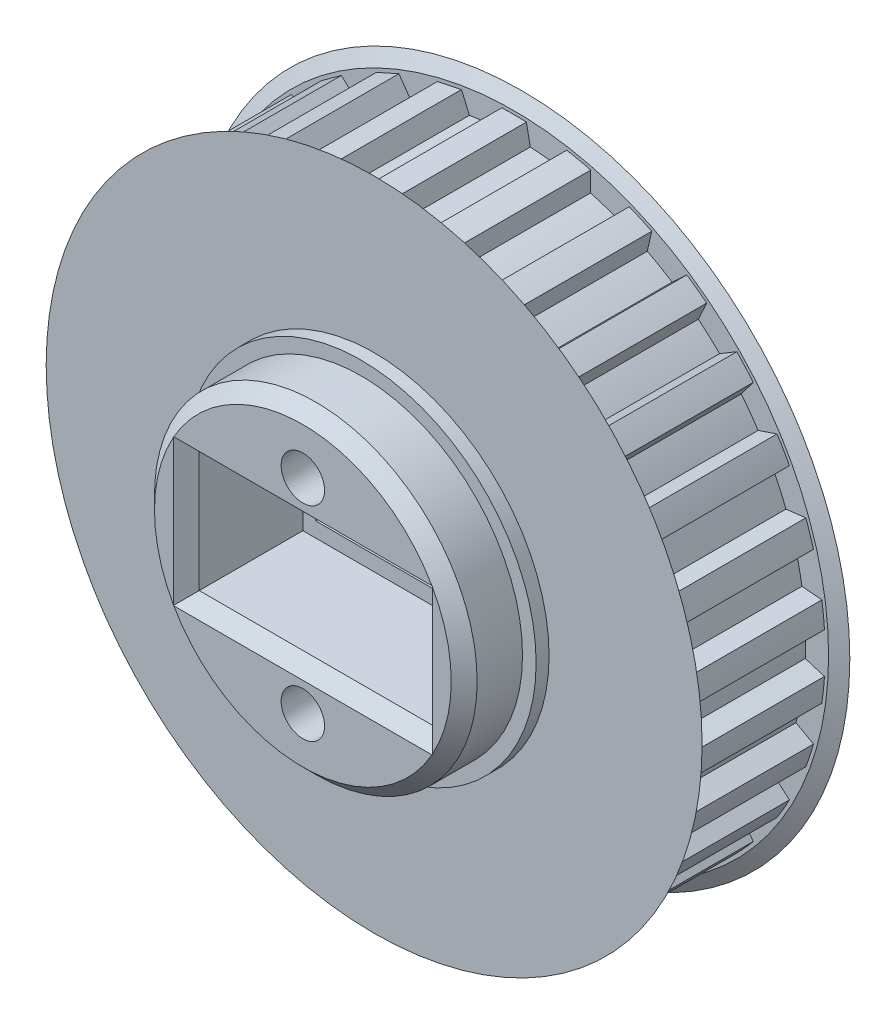
SolidWorks part; units mm, degrees
material "ABS"
ref_plane "Alzado" through (0, 0, 0) normal (0, 0, 1) x (1, 0, 0)
ref_plane "Planta" through (0, 0, 0) normal (0, 1, 0) x (1, 0, 0)
ref_plane "Vista lateral" through (0, 0, 0) normal (1, 0, 0) x (0, 0, -1)
sketch "Croquis1" plane through (0, 0, 0) normal (0, 0, 1) x (1, 0, 0)
  line L0 (0, 0) -> (0, 14.5885) construction
  line L1 (-0.95, 23.9812) -> (-1.25, 22.4653)
  line L2 (0.95, 23.9812) -> (1.25, 22.4653)
  line L3 (5.9152, 23.2596) -> (5.8935, 21.7144)
  line L4 (4.0567, 23.6547) -> (3.4481, 22.2342)
  line L5 (10.6219, 21.5215) -> (10.2794, 20.0146)
  line L6 (8.8862, 22.2943) -> (7.9955, 21.0314)
  line L7 (14.8644, 18.8428) -> (14.216, 17.44)
  line L8 (13.3272, 19.9596) -> (12.1935, 18.9095)
  line L9 (18.4572, 15.3406) -> (17.5313, 14.1033)
  line L10 (17.1858, 16.7525) -> (15.8585, 15.9611)
  line L11 (21.2433, 11.1679) -> (20.0805, 10.1501)
  line L12 (20.2933, 12.8133) -> (18.8305, 12.3152)
  line L13 (23.101, 6.5071) -> (21.752, 5.7533)
  line L14 (22.5139, 8.3141) -> (20.9795, 8.131)
  line L15 (23.9491, 1.5619) -> (22.4728, 1.1051)
  line L16 (23.7505, 3.4515) -> (22.2115, 3.5914)
  line L17 (23.7505, -3.4515) -> (22.2115, -3.5914)
  line L18 (23.9491, -1.5619) -> (22.4728, -1.1051)
  line L19 (22.5139, -8.3141) -> (20.9795, -8.131)
  line L20 (23.101, -6.5071) -> (21.752, -5.7533)
  line L21 (20.2933, -12.8133) -> (18.8305, -12.3152)
  line L22 (21.2433, -11.1679) -> (20.0805, -10.1501)
  line L23 (17.1858, -16.7525) -> (15.8585, -15.9611)
  line L24 (18.4572, -15.3406) -> (17.5313, -14.1033)
  line L25 (13.3272, -19.9596) -> (12.1935, -18.9095)
  line L26 (14.8644, -18.8428) -> (14.216, -17.44)
  line L27 (8.8862, -22.2943) -> (7.9955, -21.0314)
  line L28 (10.6219, -21.5215) -> (10.2794, -20.0146)
  line L29 (4.0567, -23.6547) -> (3.4481, -22.2342)
  line L30 (5.9152, -23.2596) -> (5.8935, -21.7144)
  line L31 (-0.95, -23.9812) -> (-1.25, -22.4653)
  line L32 (0.95, -23.9812) -> (1.25, -22.4653)
  line L33 (-5.9152, -23.2596) -> (-5.8935, -21.7144)
  line L34 (-4.0567, -23.6547) -> (-3.4481, -22.2342)
  line L35 (-10.6219, -21.5215) -> (-10.2794, -20.0146)
  line L36 (-8.8862, -22.2943) -> (-7.9955, -21.0314)
  line L37 (-14.8644, -18.8428) -> (-14.216, -17.44)
  line L38 (-13.3272, -19.9596) -> (-12.1935, -18.9095)
  line L39 (-18.4572, -15.3406) -> (-17.5313, -14.1033)
  line L40 (-17.1858, -16.7525) -> (-15.8585, -15.9611)
  line L41 (-21.2433, -11.1679) -> (-20.0805, -10.1501)
  line L42 (-20.2933, -12.8133) -> (-18.8305, -12.3152)
  line L43 (-23.101, -6.5071) -> (-21.752, -5.7533)
  line L44 (-22.5139, -8.3141) -> (-20.9795, -8.131)
  line L45 (-23.9491, -1.5619) -> (-22.4728, -1.1051)
  line L46 (-23.7505, -3.4515) -> (-22.2115, -3.5914)
  line L47 (-23.7505, 3.4515) -> (-22.2115, 3.5914)
  line L48 (-23.9491, 1.5619) -> (-22.4728, 1.1051)
  line L49 (-22.5139, 8.3141) -> (-20.9795, 8.131)
  line L50 (-23.101, 6.5071) -> (-21.752, 5.7533)
  line L51 (-20.2933, 12.8133) -> (-18.8305, 12.3152)
  line L52 (-21.2433, 11.1679) -> (-20.0805, 10.1501)
  line L53 (-17.1858, 16.7525) -> (-15.8585, 15.9611)
  line L54 (-18.4572, 15.3406) -> (-17.5313, 14.1033)
  line L55 (-13.3272, 19.9596) -> (-12.1935, 18.9095)
  line L56 (-14.8644, 18.8428) -> (-14.216, 17.44)
  line L57 (-18.4572, 15.3406) -> (-17.1858, 16.7525)
  line L58 (-14.8644, 18.8428) -> (-13.3272, 19.9596)
  line L59 (-8.8862, 22.2943) -> (-7.9955, 21.0314)
  line L60 (-10.6219, 21.5215) -> (-10.2794, 20.0146)
  line L61 (-4.0567, 23.6547) -> (-3.4481, 22.2342)
  line L62 (-5.9152, 23.2596) -> (-5.8935, 21.7144)
  line L63 (-10.6219, 21.5215) -> (-8.8862, 22.2943)
  line L64 (-5.9152, 23.2596) -> (-4.0567, 23.6547)
  arc A0 (-17.5313, 14.1033) -> (-18.8305, 12.3152) centre (0, 0) ccw
  arc A1 (3.4481, 22.2342) -> (1.25, 22.4653) centre (0, 0) ccw
  arc A2 (-14.216, 17.44) -> (-15.8585, 15.9611) centre (0, 0) ccw
  arc A3 (-5.8935, 21.7144) -> (-7.9955, 21.0314) centre (0, 0) ccw
  arc A4 (-10.2794, 20.0146) -> (-12.1935, 18.9095) centre (0, 0) ccw
  arc A8 (-20.2933, 12.8133) -> (-21.2433, 11.1679) centre (0, 0) ccw
  arc A9 (-22.5139, 8.3141) -> (-23.101, 6.5071) centre (0, 0) ccw
  arc A10 (-23.7505, 3.4515) -> (-23.9491, 1.5619) centre (0, 0) ccw
  arc A11 (5.9152, 23.2596) -> (4.0567, 23.6547) centre (0, 0) ccw
  arc A12 (0.95, 23.9812) -> (-0.95, 23.9812) centre (0, 0) ccw
  arc A16 (10.6219, 21.5215) -> (8.8862, 22.2943) centre (0, 0) ccw
  arc A17 (14.8644, 18.8428) -> (13.3272, 19.9596) centre (0, 0) ccw
  arc A18 (18.4572, 15.3406) -> (17.1858, 16.7525) centre (0, 0) ccw
  arc A19 (21.2433, 11.1679) -> (20.2933, 12.8133) centre (0, 0) ccw
  arc A20 (23.101, 6.5071) -> (22.5139, 8.3141) centre (0, 0) ccw
  arc A21 (23.9491, 1.5619) -> (23.7505, 3.4515) centre (0, 0) ccw
  arc A22 (23.7505, -3.4515) -> (23.9491, -1.5619) centre (0, 0) ccw
  arc A23 (22.5139, -8.3141) -> (23.101, -6.5071) centre (0, 0) ccw
  arc A24 (20.2933, -12.8133) -> (21.2433, -11.1679) centre (0, 0) ccw
  arc A25 (17.1858, -16.7525) -> (18.4572, -15.3406) centre (0, 0) ccw
  arc A26 (-0.95, -23.9812) -> (0.95, -23.9812) centre (0, 0) ccw
  arc A27 (-5.9152, -23.2596) -> (-4.0567, -23.6547) centre (0, 0) ccw
  arc A28 (-10.6219, -21.5215) -> (-8.8862, -22.2943) centre (0, 0) ccw
  arc A29 (-18.4572, -15.3406) -> (-17.1858, -16.7525) centre (0, 0) ccw
  arc A30 (-21.2433, -11.1679) -> (-20.2933, -12.8133) centre (0, 0) ccw
  arc A31 (-23.101, -6.5071) -> (-22.5139, -8.3141) centre (0, 0) ccw
  arc A32 (-23.9491, -1.5619) -> (-23.7505, -3.4515) centre (0, 0) ccw
  arc A33 (4.0567, -23.6547) -> (5.9152, -23.2596) centre (0, 0) ccw
  arc A34 (8.8862, -22.2943) -> (10.6219, -21.5215) centre (0, 0) ccw
  arc A35 (13.3272, -19.9596) -> (14.8644, -18.8428) centre (0, 0) ccw
  arc A36 (7.9955, 21.0314) -> (5.8935, 21.7144) centre (0, 0) ccw
  arc A37 (12.1935, 18.9095) -> (10.2794, 20.0146) centre (0, 0) ccw
  arc A39 (-1.25, 22.4653) -> (-3.4481, 22.2342) centre (0, 0) ccw
  arc A43 (15.8585, 15.9611) -> (14.216, 17.44) centre (0, 0) ccw
  arc A44 (18.8305, 12.3152) -> (17.5313, 14.1033) centre (0, 0) ccw
  arc A45 (20.9795, 8.131) -> (20.0805, 10.1501) centre (0, 0) ccw
  arc A46 (22.2115, 3.5914) -> (21.752, 5.7533) centre (0, 0) ccw
  arc A47 (22.4728, -1.1051) -> (22.4728, 1.1051) centre (0, 0) ccw
  arc A48 (21.752, -5.7533) -> (22.2115, -3.5914) centre (0, 0) ccw
  arc A49 (20.0805, -10.1501) -> (20.9795, -8.131) centre (0, 0) ccw
  arc A50 (17.5313, -14.1033) -> (18.8305, -12.3152) centre (0, 0) ccw
  arc A51 (14.216, -17.44) -> (15.8585, -15.9611) centre (0, 0) ccw
  arc A52 (10.2794, -20.0146) -> (12.1935, -18.9095) centre (0, 0) ccw
  arc A53 (5.8935, -21.7144) -> (7.9955, -21.0314) centre (0, 0) ccw
  arc A54 (1.25, -22.4653) -> (3.4481, -22.2342) centre (0, 0) ccw
  arc A55 (-3.4481, -22.2342) -> (-1.25, -22.4653) centre (0, 0) ccw
  arc A56 (-7.9955, -21.0314) -> (-5.8935, -21.7144) centre (0, 0) ccw
  arc A57 (-12.1935, -18.9095) -> (-10.2794, -20.0146) centre (0, 0) ccw
  arc A58 (-15.8585, -15.9611) -> (-14.216, -17.44) centre (0, 0) ccw
  arc A59 (-18.8305, -12.3152) -> (-17.5313, -14.1033) centre (0, 0) ccw
  arc A60 (-20.9795, -8.131) -> (-20.0805, -10.1501) centre (0, 0) ccw
  arc A61 (-22.2115, -3.5914) -> (-21.752, -5.7533) centre (0, 0) ccw
  arc A62 (-22.4728, 1.1051) -> (-22.4728, -1.1051) centre (0, 0) ccw
  arc A63 (-21.752, 5.7533) -> (-22.2115, 3.5914) centre (0, 0) ccw
  arc A64 (-20.0805, 10.1501) -> (-20.9795, 8.131) centre (0, 0) ccw
  arc A71 (-14.8644, -18.8428) -> (-13.3272, -19.9596) centre (0, 0) ccw
  circle A72 centre (0, 0) radius 1.5
  point P151 (0, 0)
  dimension "D1" = 24
  dimension "D6" = 3
  dimension "D5" = 1.5
  dimension "D2" = 2.5
  dimension "D3" = 1.9
  dimension "D4" = 30
extrude "Saliente-Extruir1" add sketch "Croquis1" along normal blind 10.2
sketch "Croquis2" plane through (0, 0, 10.2) normal (0, 0, 1) x (1, 0, 0)
  circle A0 centre (0, 0) radius 26
  circle A1 centre (0, 0) radius 1.5
  circle A2 centre (0, 0) radius 1.5 construction
  dimension "D1" = 52
extrude "Saliente-Extruir2" add sketch "Croquis2" along normal blind 0.6
sketch "Croquis3" plane through (0, 0, 10.8) normal (0, 0, 1) x (1, 0, 0)
  circle A0 centre (0, 0) radius 1.5
  circle A1 centre (0, 0) radius 12.45
  circle A3 centre (0, 0) radius 1.5 construction
  dimension "D1" = 24.9
sketch "Croquis4" plane through (0, 0, 0) normal (0, 0, -1) x (-1, 0, 0)
  circle A0 centre (0, 0) radius 1.5
  circle A1 centre (0, 0) radius 12.45
  circle A2 centre (0, 0) radius 1.5 construction
  dimension "D1" = 24.9
extrude "Saliente-Extruir4" add sketch "Croquis4" along normal blind 4.25
sketch "Croquis6" plane through (0, 0, 0) normal (0, 0, -1) x (-1, 0, 0)
  circle A0 centre (0, 0) radius 26
  circle A1 centre (0, 0) radius 1.5
  circle A2 centre (0, 0) radius 1.5 construction
  dimension "D1" = 52
extrude "Saliente-Extruir6" add sketch "Croquis6" along normal blind 0.6
sketch "Croquis5" plane through (0, 0, -0.6) normal (0, 0, -1) x (-1, 0, 0)
  circle A0 centre (0, 0) radius 1.5
  circle A1 centre (0, 0) radius 13.5
  circle A2 centre (0, 0) radius 1.5 construction
  dimension "D1" = 27
extrude "Saliente-Extruir5" add sketch "Croquis5" along normal blind 1.6
chamfer "Chaflán2" distance 1 angle 60 2 edges at (-26, 0, 0) (26, 0, 10.2)
extrude "Saliente-Extruir7" add sketch "Croquis3" along normal blind 5.5
chamfer "Chaflán4" distance 1 angle 45 1 edges at (12.45, 0, 16.3)
sketch "Croquis7" plane through (0, 0, 10.8) normal (0, 0, 1) x (1, 0, 0)
  circle A0 centre (0, 0) radius 1.5
  circle A1 centre (0, 0) radius 13.5
  circle A2 centre (0, 0) radius 1.5 construction
  dimension "D1" = 27
extrude "Saliente-Extruir8" add sketch "Croquis7" along normal blind 1
sketch "Croquis8" plane through (0, 0, 0) normal (0, 0, 1) x (1, 0, 0)
  line L0 (0, 0) -> (6.706, 0) construction
  line L1 (-8, 3.5) -> (8, 3.5)
  line L2 (-8, 3.5) -> (-8, -3.5)
  line L3 (-8, -3.5) -> (8, -3.5)
  line L4 (8, 3.5) -> (8, -3.5)
  line L5 (-8, 3.5) -> (8, -3.5) construction
  line L6 (-8, -3.5) -> (8, 3.5) construction
  circle A0 centre (0, 7.8756) radius 1.675
  circle A1 centre (0, -7.8756) radius 1.675
  point P0 (0, 0)
  dimension "D1" = 3.35
  dimension "D2" = 7
  dimension "D3" = 16
extrude "Cortar-Extruir1" cut sketch "Croquis8" against normal through all both and the other way through all
sketch "Croquis10" plane through (0, 0, 16.3) normal (0, 0, 1) x (1, 0, 0)
  line L1 (9, 4.65) -> (-9, 4.65)
  line L2 (9, 4.65) -> (9, -4.65)
  line L3 (9, -4.65) -> (-9, -4.65)
  line L4 (-9, 4.65) -> (-9, -4.65)
  line L5 (9, 4.65) -> (-9, -4.65) construction
  line L6 (9, -4.65) -> (-9, 4.65) construction
  point P0 (0, 0)
  dimension "D1" = 9.3
  dimension "D2" = 18
extrude "Cortar-Extruir3" cut sketch "Croquis10" against normal blind 9
chamfer "Chaflán5" distance 1 angle 45 8 edges at (-8, 0, -4.25) (0, 3.5, -4.25) (8, 0, -4.25) (0, -3.5, -4.25) (9, 0, 16.3) (0, 4.65, 16.3) (-9, 0, 16.3) (0, -4.65, 16.3)
sketch "Sketch1" plane through (0, 0, -4.25) normal (0, 0, -1) x (-1, 0, 0)
  circle A0 centre (0, 0) radius 12.45
  circle A1 centre (0, 0) radius 12.45 construction
  circle A2 centre (0, 7.8756) radius 1.675
  circle A3 centre (0, -7.8756) radius 1.675
  circle A4 centre (0, 7.8756) radius 1.675 construction
extrude "Boss-Extrude1" add sketch "Sketch1" against normal blind 5
sketch "Sketch2" plane through (0, 0, -4.25) normal (0, 0, -1) x (-1, 0, 0)
  line L0 (0, 17.274) -> (0, -20.0751) construction
  line L1 (-7.363, 0) -> (7.363, 0) construction
  circle A0 centre (-7.363, 0) radius 1.45
  circle A1 centre (7.363, 0) radius 1.45
  dimension "D1" = 2.9
  dimension "D2" = 14.726
extrude "Cut-Extrude1" cut sketch "Sketch2" against normal blind 5
sketch "Sketch4" plane through (0, 0, 16.3) normal (0, 0, 1) x (1, 0, 0)
  line L0 (-8, -3.5) -> (8, -3.5) construction
  line L1 (4, 3.5) -> (-4, 3.5)
  line L2 (4, 3.5) -> (4, -3.5)
  line L3 (4, -3.5) -> (-4, -3.5)
  line L4 (-4, 3.5) -> (-4, -3.5)
  line L5 (4, 3.5) -> (-4, -3.5) construction
  line L6 (4, -3.5) -> (-4, 3.5) construction
  point P0 (0, 0)
  dimension "D1" = 8
extrude "Cut-Extrude2" cut sketch "Sketch4" against normal blind 21
chamfer "Chamfer3" distance 1 angle 45 4 edges at (-4, 0, -4.25) (0, 3.5, -4.25) (4, 0, -4.25) (0, -3.5, -4.25)
chamfer "Chamfer2" distance 0.75 angle 45 1 edges at (-12.45, 0, -4.25)
